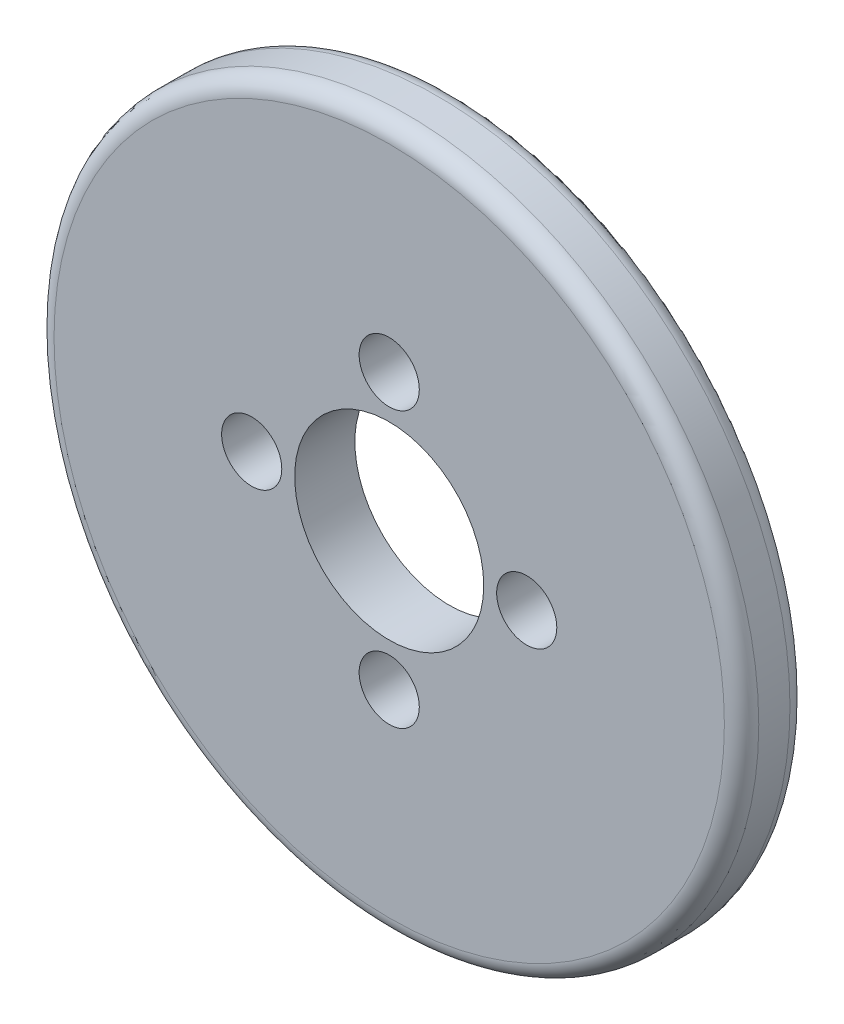
SolidWorks part; units mm, degrees
material "ABS"
ref_plane "Front Plane" through (0, 0, 0) normal (0, 0, 1) x (1, 0, 0)
ref_plane "Top Plane" through (0, 0, 0) normal (0, 1, 0) x (1, 0, 0)
ref_plane "Right Plane" through (0, 0, 0) normal (1, 0, 0) x (0, 0, -1)
sketch "Sketch1" plane through (0, 0, 0) normal (0, 0, 1) x (1, 0, 0)
  circle A0 centre (0, 0) radius 5.5
  circle A2 centre (0, 0) radius 20.5
  dimension "D1" = 11
  dimension "D2" = 15
extrude "Boss-Extrude1" add sketch "Sketch1" along normal blind 3.5
sketch "Sketch8" plane through (0, 0, 0) normal (0, 1, 0) x (1, 0, 0)
  line L0 (20.5, 0) -> (-20.5, 0) construction
  line L1 (20.5, 0) -> (-11.5, 0) construction
  line L2 (0, 0) -> (0, -17.1822) construction
  line L3 (-11.5, 0) -> (-11.5, 3.5)
  line L4 (-11.5, 3.5) -> (20.5, 0) construction
  line L5 (11.5, 3.5) -> (-20.5, 0) construction
  line L6 (11.5, 0) -> (11.5, 3.5) construction
  line L7 (11.5, 0) -> (-20.5, 0) construction
  line L8 (-11.5, 3.5) -> (-20.5, 0)
  line L9 (-20.5, 0) -> (-11.5, 0)
  point P10 (11.5, 1.75)
  dimension "D1" = 23
  dimension "D2" = 3.5
revolve "Revolve2" add sketch "Sketch8" angle 360 about L2
sketch "Sketch7" plane through (0, 0, 0) normal (0, 0, 1) x (1, 0, 0)
  circle A0 centre (0, 0) radius 8 construction
  circle A1 centre (0, -8) radius 1.75
  circle A5 centre (-8, 0) radius 1.75
  circle A6 centre (0, 8) radius 1.75
  circle A7 centre (8, 0) radius 1.75
  point P5 (-8, 0)
  point P14 (0, 0)
  point P15 (0, 0)
  dimension "D1" = 16
  dimension "D2" = 3.5
  dimension "D3" = 4
extrude "Cut-Extrude1" cut sketch "Sketch7" along normal up to surface (3.5 mm away) contours A7 | A1 | A6 | A5 region at (8, 0, 0) up to face at (20.5, 0, 3.5)
fillet "Fillet2" radius 1 2 edges at (20.5, 0, 3.5) (-20.5, 0, 0)
